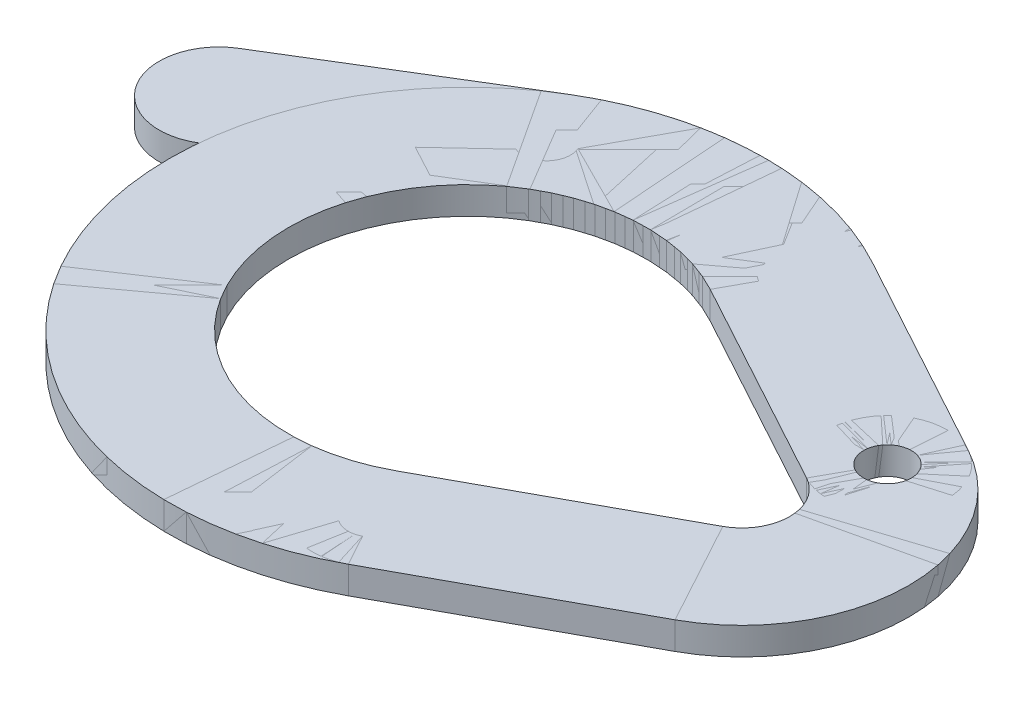
SolidWorks part; units mm, degrees
ref_plane "Front Plane" through (0, 0, 0) normal (0, 0, 1) x (1, 0, 0)
ref_plane "Top Plane" through (0, 0, 0) normal (0, 1, 0) x (1, 0, 0)
ref_plane "Right Plane" through (0, 0, 0) normal (1, 0, 0) x (0, 0, -1)
sketch "Sketch7" plane through (0, 0, 0) normal (0, 1, 0) x (1, 0, 0)
  line L0 (9.5652, -17.5644) -> (27.3043, -7.904) construction
  line L1 (27.3043, 7.904) -> (9.5652, 17.5644) construction
  line L2 (9.5652, 17.5644) -> (-9.9678, 28.2017) construction
  line L3 (9.5652, 17.5644) -> (0, 0) construction
  line L4 (0, 0) -> (9.5652, -17.5644) construction
  line L5 (27.3043, -7.904) -> (23, 0) construction
  line L6 (23, 0) -> (27.3043, 7.904) construction
  line L7 (0, 0) -> (-10.4286, 17.0659) construction
  line L8 (-10.4286, 17.0659) -> (-45.7887, -4.5419) construction
  circle A0 centre (0, 0) radius 15 construction
  circle A1 centre (23, 0) radius 4 construction
  arc A3 (9.5652, -17.5644) -> (9.5652, 17.5644) centre (0, 0) cw construction
  arc A4 (27.3043, -7.904) -> (27.3043, 7.904) centre (23, 0) ccw construction
  point P5 (-45.7887, -4.5419)
  dimension "D1" = 30
  dimension "D2" = 8
  dimension "D4" = 20
  dimension "D5" = 9
  dimension "D3" = 23
  dimension "D6" = 122.856
  dimension "D7" = 122.856
  dimension "D8" = 60
sketch "Sketch8" plane through (0, 0, 0) normal (0, 1, 0) x (1, 0, 0)
  arc A0 (9.5652, 17.5644) -> (9.5652, -17.5644) centre (0, 0) ccw construction
  arc A1 (9.5652, 17.5644) -> (9.5652, -17.5644) centre (0, 0) ccw construction
  arc A2 (11.9565, 21.9554) -> (11.9565, -21.9554) centre (0, 0) ccw
  arc A3 (7.1739, 13.1733) -> (7.1739, -13.1733) centre (0, 0) ccw
  arc A4 (11.9565, 21.9554) -> (7.1739, 13.1733) centre (9.5652, 17.5644) cw
  arc A5 (11.9565, -21.9554) -> (7.1739, -13.1733) centre (9.5652, -17.5644) ccw
  circle A6 centre (9.5652, 17.5644) radius 2
  circle A7 centre (9.5652, -17.5644) radius 2
  dimension "D3" = 4
  dimension "D1" = 5
  dimension "D2" = 5
base flange "Base-Flange2" sketch "Sketch8" thickness 2.3 reverse thickness direction no parameters "D1"=0.7366
sketch "Sketch11" plane through (0, 0, 0) normal (0, 1, 0) x (1, 0, 0)
  line L0 (9.5652, -17.5644) -> (27.3043, -7.904) construction
  line L1 (11.9565, -21.9554) -> (29.6957, -12.295)
  line L2 (7.1739, -13.1733) -> (24.913, -3.5129)
  arc A0 (27.3043, -7.904) -> (27.3043, 7.904) centre (23, 0) ccw construction
  arc A1 (27.3043, -7.904) -> (27.3043, 7.904) centre (23, 0) ccw construction
  arc A2 (29.6957, -12.295) -> (29.6957, 12.295) centre (23, 0) ccw
  arc A3 (24.913, -3.5129) -> (24.913, 3.5129) centre (23, 0) ccw
  arc A4 (11.9565, -21.9554) -> (7.1739, -13.1733) centre (9.5652, -17.5644) cw
  arc A5 (29.6957, 12.295) -> (24.913, 3.5129) centre (27.3043, 7.904) ccw
  circle A6 centre (27.3043, 7.904) radius 2
  circle A7 centre (9.5652, -17.5644) radius 2
  dimension "D3" = 4
  dimension "D1" = 5
  dimension "D2" = 5
sketch "Sketch14" plane through (0, 0, 0) normal (0, 1, 0) x (1, 0, 0)
  line L0 (27.3043, 7.904) -> (9.5652, 17.5644) construction
  line L1 (0, 0) -> (-10.4286, 17.0659) construction
  line L2 (0, 0) -> (9.5652, 17.5644) construction
  line L3 (29.6957, 12.295) -> (11.9565, 21.9554)
  line L4 (24.913, 3.5129) -> (7.1739, 13.1733)
  arc A0 (9.5652, 17.5644) -> (-10.4286, 17.0659) centre (0, 0) ccw construction
  arc A1 (11.9565, 21.9554) -> (-13.0357, 21.3324) centre (0, 0) ccw
  arc A2 (7.1739, 13.1733) -> (-7.8214, 12.7994) centre (0, 0) ccw
  arc A3 (29.6957, 12.295) -> (24.913, 3.5129) centre (27.3043, 7.904) cw
  arc A4 (-13.0357, 21.3324) -> (-7.8214, 12.7994) centre (-10.4286, 17.0659) ccw
  circle A5 centre (-10.4286, 17.0659) radius 2
  circle A6 centre (27.3043, 7.904) radius 2
  dimension "D4" = 4
  dimension "D1" = 60
  dimension "D2" = 5
  dimension "D3" = 5
base flange "Base-Flange4" sketch "Sketch14" thickness 2.3 reverse thickness direction no parameters "D1"=0.7366
sketch "Sketch17" plane through (0, 0, 0) normal (0, 1, 0) x (1, 0, 0)
  line L0 (0, 0) -> (-10.4286, 17.0659) construction
  line L2 (-10.4286, 17.0659) -> (-27.4945, 6.6373) construction
  line L3 (-10.4286, 17.0659) -> (-45.7887, -4.5419) construction
  line L4 (-13.0357, 21.3324) -> (-30.1016, 10.9038)
  line L5 (-7.8214, 12.7994) -> (-24.8873, 2.3709)
  arc A1 (9.5652, 17.5644) -> (-10.4286, 17.0659) centre (0, 0) ccw construction
  arc A2 (11.9565, 21.9554) -> (-13.0357, 21.3324) centre (0, 0) ccw
  arc A3 (7.1739, 13.1733) -> (-7.8214, 12.7994) centre (0, 0) ccw
  arc A4 (11.9565, 21.9554) -> (7.1739, 13.1733) centre (9.5652, 17.5644) cw
  arc A5 (-30.1016, 10.9038) -> (-24.8873, 2.3709) centre (-27.4945, 6.6373) ccw
  circle A7 centre (9.5652, 17.5644) radius 2
  circle A8 centre (-10.4286, 17.0659) radius 2
  dimension "D4" = 4
  dimension "D1" = 20
  dimension "D2" = 5
  dimension "D3" = 5
base flange "Base-Flange5" sketch "Sketch17" thickness 2.3 reverse thickness direction no parameters "D1"=0.7366
base flange "Base-Flange6" sketch "Sketch11" thickness 2.3 reverse thickness direction no parameters "D1"=0.7366
sketch "Sketch23" plane through (0, 0, 0) normal (0, 1, 0) x (1, 0, 0)
  line L0 (27.3043, 7.904) -> (9.5652, 17.5644) construction
  line L1 (9.5652, -17.5644) -> (27.3043, -7.904) construction
  line L2 (11.9565, -21.9554) -> (29.6957, -12.295)
  line L3 (7.1739, -13.1733) -> (24.913, -3.5129)
  arc A0 (9.5652, 17.5644) -> (9.5652, -17.5644) centre (0, 0) ccw construction
  arc A1 (9.5652, 17.5644) -> (9.5652, -17.5644) centre (0, 0) ccw construction
  arc A2 (27.3043, -7.904) -> (27.3043, 7.904) centre (23, 0) ccw construction
  arc A3 (11.9565, 21.9554) -> (11.9565, -21.9554) centre (0, 0) ccw
  arc A4 (29.6957, -12.295) -> (29.6957, 12.295) centre (23, 0) ccw
  arc A5 (7.1739, 13.1733) -> (7.1739, -13.1733) centre (0, 0) ccw
  arc A6 (24.913, -3.5129) -> (24.913, 3.5129) centre (23, 0) ccw
  arc A7 (11.9565, 21.9554) -> (7.1739, 13.1733) centre (9.5652, 17.5644) cw
  arc A8 (29.6957, 12.295) -> (24.913, 3.5129) centre (27.3043, 7.904) ccw
  circle A9 centre (9.5652, 17.5644) radius 2
  circle A10 centre (27.3043, 7.904) radius 2
  dimension "D3" = 4
  dimension "D1" = 5
  dimension "D2" = 5
base flange "Base-Flange7" sketch "Sketch23" thickness 2.3 reverse thickness direction no parameters "D1"=0.7366
sketch "Bend-Lines1" [suppressed] plane through (0, 0, 0) normal (0, 1, 0) x (1, 0, 0)
sketch "Bounding-Box1" [suppressed] plane through (0, 0, 0) normal (0, 1, 0) x (1, 0, 0)
sheet metal parameters "Sheet-Metal2" thickness 2.3 parameters "D1"=0.7366
flat pattern "Flat-Pattern2" [suppressed]
sketch "Bend-Lines3" plane through (0, 0, 0) normal (0, 1, 0) x (1, 0, 0)
sketch3d "Bounding-Box3" [suppressed]
  line L0 (9.7825, -33.7821, 0) -> (9.7824, 16.2178, 0) construction
  line L1 (-29.7825, -33.7822, 0) -> (-29.7826, 16.2178, 0) construction
  line L2 (9.7825, -33.7821, 0) -> (-29.7825, -33.7822, 0) construction
  line L3 (9.7824, 16.2178, 0) -> (-29.7826, 16.2178, 0) construction
sheet metal parameters "Sheet-Metal4" thickness 2.3 parameters "D1"=0.7366
flat pattern "Flat-Pattern4"
sketch "Bend-Lines5" plane through (0, 0, 0) normal (0, 1, 0) x (1, 0, 0)
sketch3d "Bounding-Box5" [suppressed]
  line L0 (7.425, 9.3897, 0) -> (-40.0253, 20.9113, 0) construction
  line L1 (3.6789, -6.0386, 0) -> (-43.7715, 5.483, 0) construction
  line L2 (7.425, 9.3897, 0) -> (3.6789, -6.0386, 0) construction
  line L3 (-40.0253, 20.9113, 0) -> (-43.7715, 5.483, 0) construction
sheet metal parameters "Sheet-Metal5" thickness 2.3 parameters "D1"=0.7366
flat pattern "Flat-Pattern5"
sketch "Bend-Lines6" plane through (0, 0, 0) normal (0, 1, 0) x (1, 0, 0)
sketch3d "Bounding-Box6" [suppressed]
  line L0 (-44.9261, -1.9265, 0) -> (1.7251, 11.8287, 0) construction
  line L1 (-40.4413, -17.1369, 0) -> (6.2099, -3.3817, 0) construction
  line L2 (-44.9261, -1.9265, 0) -> (-40.4413, -17.1369, 0) construction
  line L3 (1.7251, 11.8287, 0) -> (6.2099, -3.3817, 0) construction
sheet metal parameters "Sheet-Metal7" thickness 2.3 parameters "D1"=0.7366
flat pattern "Flat-Pattern7"
sketch "Bend-Lines7" plane through (0, 0, 0) normal (0, 1, 0) x (1, 0, 0)
sketch3d "Bounding-Box7" [suppressed]
  line L0 (-6.9605, -1.2451, 0) -> (16.5249, 32.4733, 0) construction
  line L1 (9.439, -12.6676, 0) -> (32.9244, 21.0508, 0) construction
  line L2 (-6.9605, -1.2451, 0) -> (9.439, -12.6676, 0) construction
  line L3 (16.5249, 32.4733, 0) -> (32.9244, 21.0508, 0) construction
sheet metal parameters "Sheet-Metal8" thickness 2.3 parameters "D1"=0.7366
flat pattern "Flat-Pattern8"
sketch "Bend-Lines8" plane through (0, 0, 0) normal (0, 1, 0) x (1, 0, 0)
sketch3d "Bounding-Box8" [suppressed]
  line L0 (32.4255, -11.9649, 0) -> (-19.5641, 16.3476, 0) construction
  line L1 (8.5124, -55.8758, 0) -> (-43.4772, -27.5633, 0) construction
  line L2 (32.4255, -11.9649, 0) -> (8.5124, -55.8758, 0) construction
  line L3 (-19.5641, 16.3476, 0) -> (-43.4772, -27.5633, 0) construction
